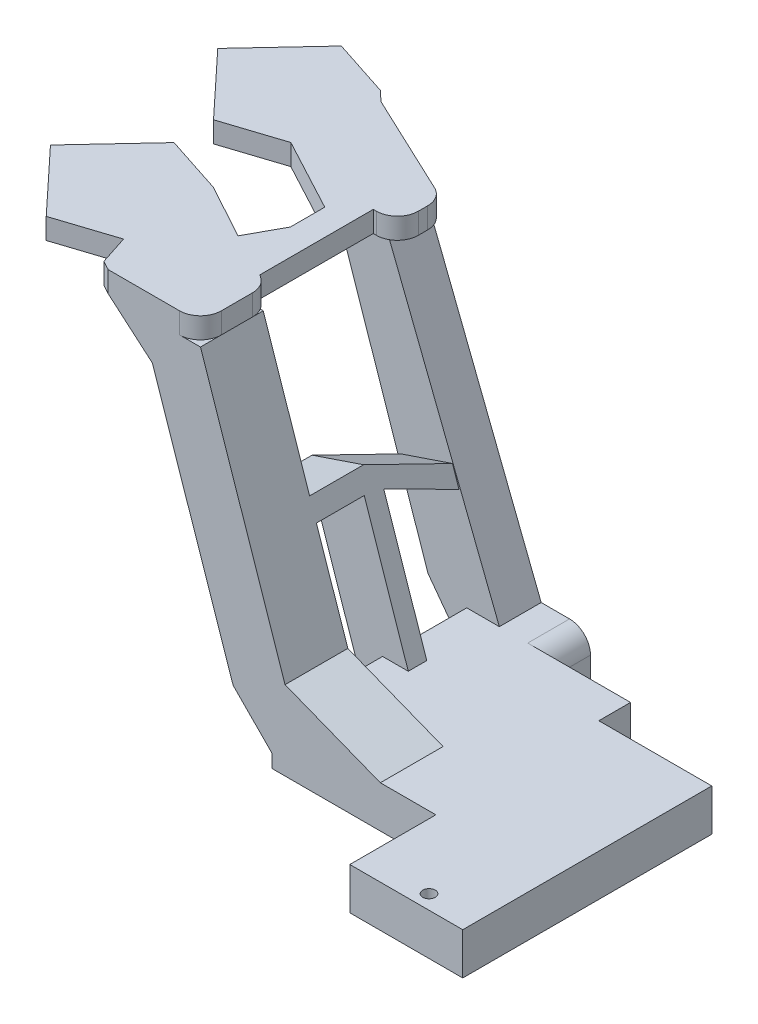
SolidWorks part; units mm, degrees
material "PET"
ref_plane "Alzado" through (0, 0, 0) normal (0, 0, 1) x (1, 0, 0)
ref_plane "Planta" through (0, 0, 0) normal (0, 1, 0) x (1, 0, 0)
ref_plane "Vista lateral" through (0, 0, 0) normal (1, 0, 0) x (0, 0, -1)
sketch "Croquis1" plane through (0, 0, 0) normal (0, 1, 0) x (1, 0, 0)
  line L0 (0, 0) -> (-147.535, 0) construction
  line L2 (-192.3148, 37.3519) -> (-153.15, 37.3519)
  line L6 (-153.15, 37.3519) -> (-153.15, 29.7699)
  line L7 (-153.15, 29.7699) -> (-126.1478, 29.7699)
  line L12 (-126.1478, 29.7699) -> (-126.1478, -29.7699)
  line L17 (-153.15, -29.7699) -> (-126.1478, -29.7699)
  line L19 (-192.3148, -9.1953) -> (-192.3148, 37.3519)
  line L21 (-192.3148, -9.1953) -> (-153.15, -9.1953)
  line L22 (-153.15, -9.1953) -> (-153.15, -29.7699)
  circle A3 centre (-137.6312, -26.3448) radius 1.5
  point P3 (-156.9577, 0.0873)
  point P17 (-126.1478, 0)
  point P22 (-156.9577, -0.0873)
  dimension "D2" = 147.535
extrude "Saliente-Extruir1" add sketch "Croquis1" along normal blind 10
sketch "Croquis3" plane through (0, 0, 9.1953) normal (0, 0, 1) x (1, 0, 0)
  line L0 (-189.1955, 0) -> (-201.6048, 12.5453)
  line L2 (-201.6048, 12.5453) -> (-220.9436, 69.6801)
  line L5 (-209.4336, 78.7242) -> (-189.1955, 18.9327)
  line L6 (-189.1955, 18.9327) -> (-166.4279, 10)
  line L9 (-189.1955, 0) -> (-166.4279, 0)
  line L12 (-166.4279, 10) -> (-166.4279, 0)
  line L13 (-220.9436, 69.6801) -> (-231.4951, 78.7242)
  line L14 (-231.4951, 78.7242) -> (-209.4336, 78.7242)
extrude "Saliente-Extruir2" add sketch "Croquis3" against normal blind 15
sketch "Croquis8" plane through (-163.9984, -55.5098, 0) normal (0.9472, 0.3206, 0) x (0, 0, -1)
  line L0 (5.8047, 102.0234) -> (5.8047, 107.1059)
  line L3 (5.8047, 78.5912) -> (5.8047, 141.7149) construction
  line L5 (5.8047, 102.0234) -> (17.2295, 102.0234)
  line L6 (17.2295, 102.0234) -> (17.2295, 62.1956)
  line L12 (17.2295, 62.1956) -> (21.6494, 62.1956)
  line L14 (21.6494, 101.2355) -> (21.6494, 62.1956)
  line L15 (41.4126, 92.2401) -> (21.6494, 101.2355)
  line L16 (41.4126, 97.1393) -> (41.4126, 92.2401)
  line L17 (41.4126, 97.1393) -> (18.7036, 107.1059)
  line L18 (5.8047, 107.1059) -> (18.7036, 107.1059)
  point P10 (0, 64.6018)
extrude "Saliente-Extruir3" add sketch "Croquis8" against normal blind 13 contours L12 region at (-193.4058, 31.3718, -21.393)
sketch "Croquis10" plane through (0, 78.7242, 0) normal (0, 1, 0) x (1, 0, 0)
  line L0 (-233.72, 49.6957) -> (-261.3301, 49.6957) construction
  line L10 (-249.9187, 64.9725) -> (-235.9805, 60.4311)
  line L11 (-264.1884, 49.6957) -> (-249.9187, 64.9725)
  line L12 (-249.9187, 34.4189) -> (-264.1884, 49.6957)
  line L13 (-235.9805, 38.9603) -> (-249.9187, 34.4189)
  line L15 (-235.9805, 60.4311) -> (-233.72, 58.2162)
  line L18 (-209.4336, -9.1953) -> (-231.4951, -9.1953) construction
  line L40 (-233.72, 58.2162) -> (-209.3805, 46.7405)
  line L42 (-249.9187, 24.9725) -> (-235.9805, 20.4311)
  line L43 (-264.1884, 9.6957) -> (-249.9187, 24.9725)
  line L44 (-249.9187, -5.5811) -> (-264.1884, 9.6957)
  line L45 (-235.9805, -1.0397) -> (-249.9187, -5.5811)
  line L46 (-235.9805, -1.0397) -> (-233.72, -7.9776)
  line L47 (-233.72, -7.9776) -> (-231.4951, -9.1953)
  line L48 (-235.9805, 20.4311) -> (-233.72, 18.2162) [skipped]
  line L49 (-210.5063, 7.2713) -> (-199.5292, 2.0957) [skipped]
  line L52 (-231.4951, 5.8047) -> (-231.4951, -9.1953) construction
  line L53 (-231.4951, -9.1953) -> (-214.4336, -9.1953)
  line L54 (-209.4336, -4.1953) -> (-209.4336, 3.2431)
  line L55 (-211.5126, 7.3012) -> (-212.2737, 7.849)
  line L56 (-212.2737, 7.849) -> (-212.2737, 34.966)
  line L57 (-212.2737, 34.966) -> (-211.5128, 34.966)
  line L58 (-235.9805, 20.4311) -> (-222.9643, 13.3077)
  line L59 (-206.5128, 39.966) -> (-206.5128, 42.218)
  line L63 (-222.9643, 13.3077) -> (-218.5316, 21.4075)
  line L64 (-218.5316, 21.4075) -> (-218.5316, 29.6238)
  line L65 (-218.5316, 29.6238) -> (-235.9805, 38.9603)
  arc A0 (-214.4336, -9.1953) -> (-209.4336, -4.1953) centre (-214.4336, -4.1953) ccw
  arc A1 (-209.4336, 3.2431) -> (-211.5126, 7.3012) centre (-214.4336, 3.2431) ccw
  arc A2 (-211.5128, 34.966) -> (-206.5128, 39.966) centre (-211.5128, 39.966) ccw
  arc A3 (-209.3805, 46.7405) -> (-206.5128, 42.218) centre (-211.5128, 42.218) cw
  point P22 (-239.7162, 6.3979)
  point P27 (-239.7162, 46.3979)
  point P51 (-209.4336, 5.8047)
  dimension "D1" = 2
  dimension "D2" = 5
extrude "Saliente-Extruir7" add sketch "Croquis10" along normal blind 5
fillet "Redondeo2" radius 10 1 edges at (-196.2527, -0.7654, -19.4394)
sketch "Croquis13" plane through (0, 0, -37.3519) normal (0, 0, -1) x (-1, 0, 0)
  line L0 (192.3148, 0) -> (201.6048, 12.5453)
  line L1 (153.15, 0) -> (192.3148, 0) construction
  line L2 (192.3148, 10) -> (192.3148, 0) construction
  line L3 (201.6048, 12.5453) -> (220.9436, 69.6801)
  line L4 (220.9436, 69.6801) -> (201.6048, 12.5453) construction
  line L5 (220.9436, 69.6801) -> (227.2124, 78.1455)
  line L6 (177.7324, 10) -> (184.5153, 10)
  line L7 (153.15, 10) -> (192.3148, 10) construction
  line L8 (184.5153, 10) -> (211.2239, 78.1455)
  line L9 (211.2239, 78.1455) -> (227.2124, 78.1455)
  line L11 (182.7324, 0) -> (192.3148, 0)
  line L12 (172.7324, 5) -> (172.7324, 0)
  line L13 (172.7324, 0) -> (182.7324, 0)
  arc A0 (177.7324, 10) -> (172.7324, 5) centre (177.7324, 5) ccw
  point P20 (172.7324, 10)
  dimension "D1" = 5
extrude "Saliente-Extruir8" add sketch "Croquis13" along normal blind 10
equation "\"80.7.00mm\"=65"
